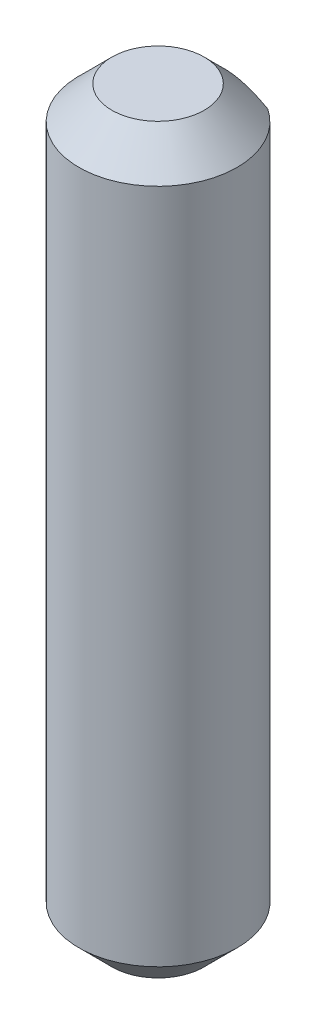
SolidWorks part; units mm, degrees
ref_plane "Front Plane" through (0, 0, 0) normal (0, 0, 1) x (1, 0, 0)
ref_plane "Top Plane" through (0, 0, 0) normal (0, 1, 0) x (1, 0, 0)
ref_plane "Right Plane" through (0, 0, 0) normal (1, 0, 0) x (0, 0, -1)
sketch "Sketch1" plane through (0, 0, 0) normal (0, 1, 0) x (1, 0, 0)
  line L0 (0, 0) -> (0, 4) construction
  line L1 (-2.6533, 4) -> (2.6533, 4)
  arc A0 (-2.6533, 4) -> (2.6533, 4) centre (0, 0) ccw
  point P7 (0, 4)
  dimension "D1" = 9.6
  dimension "D2" = 4
extrude "Boss-Extrude1" add sketch "Sketch1" along normal blind 45
chamfer "Chamfer1" distance 2 angle 45 2 edges at (0, 0, 4.8) (0, 45, 4.8)
